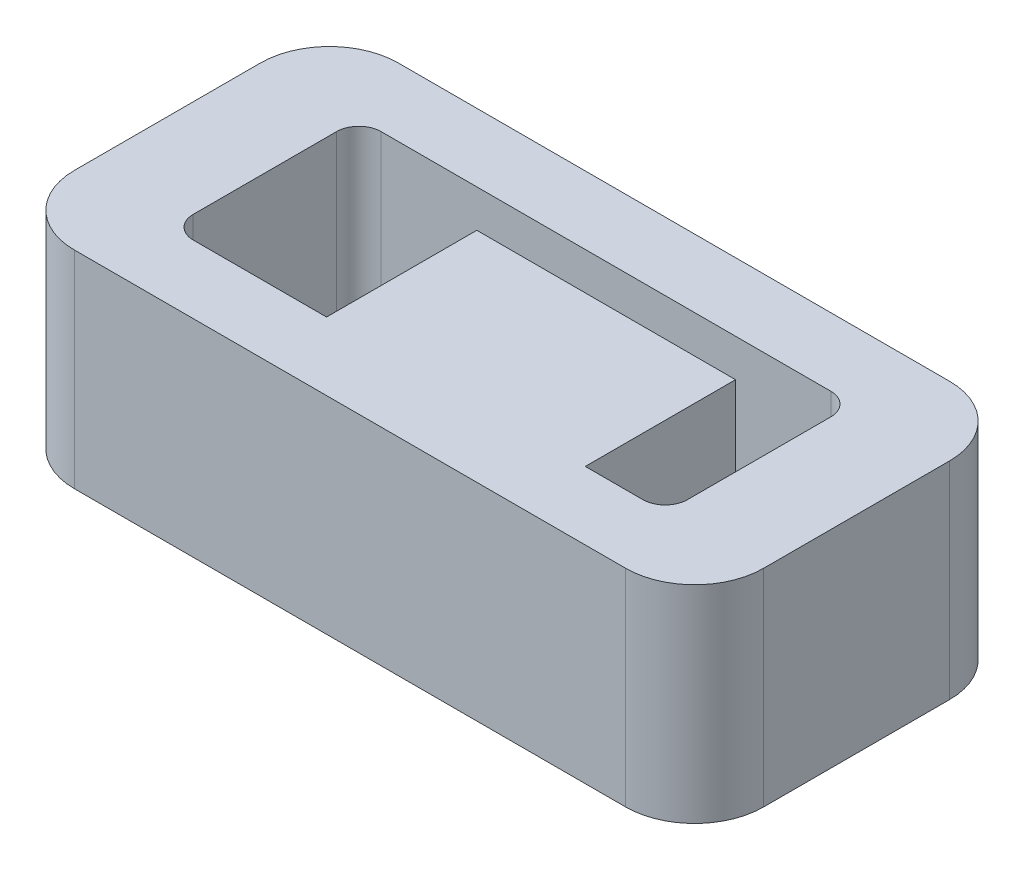
SolidWorks part; units mm, degrees
material "K110"
ref_plane "Front Plane" through (0, 0, 0) normal (0, 0, 1) x (1, 0, 0)
ref_plane "Top Plane" through (0, 0, 0) normal (0, 1, 0) x (1, 0, 0)
ref_plane "Right Plane" through (0, 0, 0) normal (1, 0, 0) x (0, 0, -1)
sketch "Sketch2" plane through (0, 0, 0) normal (0, 1, 0) x (1, 0, 0)
  line L1 (-50, -23.5) -> (50, -23.5)
  line L2 (-50, -23.5) -> (-50, 23.5)
  line L3 (-50, 23.5) -> (50, 23.5)
  line L4 (50, -23.5) -> (50, 23.5)
  line L5 (-50, -23.5) -> (50, 23.5) construction
  line L6 (-50, 23.5) -> (50, -23.5) construction
  point P0 (0, 0)
  dimension "D1" = 100
  dimension "D2" = 47
extrude "Boss-Extrude1" add sketch "Sketch2" against normal blind 30
fillet "Fillet1" radius 10 4 edges at (-50, -15, -23.5) (50, -15, -23.5) (50, -15, 23.5) (-50, -15, 23.5)
sketch "Sketch3" plane through (0, 0, 0) normal (0, 1, 0) x (1, 0, 0)
  line L16 (35.855, -10.4) -> (35.855, 10.4)
  line L17 (24.265, -13.63) -> (32.625, -13.63)
  line L18 (24.265, 8.17) -> (24.265, -13.63)
  line L19 (-13.275, 8.17) -> (24.265, 8.17)
  line L20 (-13.275, -13.63) -> (-13.275, 8.17)
  line L21 (-32.625, -13.63) -> (-13.275, -13.63)
  line L22 (-35.855, 10.4) -> (-35.855, -10.4)
  line L23 (32.625, 13.63) -> (-32.625, 13.63)
  line L24 (35.855, -10.4) -> (35.855, 10.4)
  line L25 (24.265, -13.63) -> (32.625, -13.63)
  line L26 (24.265, 8.17) -> (24.265, -13.63)
  line L27 (-13.275, 8.17) -> (24.265, 8.17)
  line L28 (-13.275, -13.63) -> (-13.275, 8.17)
  line L29 (-32.625, -13.63) -> (-13.275, -13.63)
  line L30 (-35.855, 10.4) -> (-35.855, -10.4)
  line L31 (32.625, 13.63) -> (-32.625, 13.63)
  arc A8 (35.855, 10.4) -> (32.625, 13.63) centre (32.625, 10.4) ccw
  arc A9 (32.625, -13.63) -> (35.855, -10.4) centre (32.625, -10.4) ccw
  arc A10 (-35.855, -10.4) -> (-32.625, -13.63) centre (-32.625, -10.4) ccw
  arc A11 (-32.625, 13.63) -> (-35.855, 10.4) centre (-32.625, 10.4) ccw
  arc A12 (35.855, 10.4) -> (32.625, 13.63) centre (32.625, 10.4) ccw
  arc A13 (32.625, -13.63) -> (35.855, -10.4) centre (32.625, -10.4) ccw
  arc A14 (-35.855, -10.4) -> (-32.625, -13.63) centre (-32.625, -10.4) ccw
  arc A15 (-32.625, 13.63) -> (-35.855, 10.4) centre (-32.625, 10.4) ccw
  dimension "D1" = 0.23
extrude "Cut-Extrude1" cut sketch "Sketch3" against normal up to next
hole_wizard "M6 Tapped Hole1" positions "Sketch6" profile "Sketch5" tap size "M6" standard "ISO"
sketch "Sketch6" plane through (0, -30, 0) normal (0, -1, 0) x (-1, 0, 0)
  line L0 (-50, -13.5) -> (-50, 13.5) construction
  line L1 (-40, 23.5) -> (40, 23.5) construction
  line L2 (40, -23.5) -> (-40, -23.5) construction
  line L3 (50, 13.5) -> (50, -13.5) construction
  point P0 (-43, 16.5)
  point P2 (43, 16.5)
  point P4 (43, -16.5)
  point P6 (-43, -16.5)
  point P9 (0, 0)
  point P10 (0, 0)
  point P11 (0, 0)
  point P12 (0, 0)
  dimension "D1" = 7
  dimension "D2" = 7
  dimension "D3" = 7
  dimension "D4" = 7
sketch "Sketch5" plane through (43, -30, -16.5) normal (1, 0, 0) x (0, 0, -1)
  line L0 (0, 0) -> (0, 18.5022)
  line L1 (0, 18.5022) -> (2.5, 17)
  line L2 (2.5, 17) -> (2.5, 0.525)
  line L3 (2.5, 0.525) -> (3.025, 0)
  line L5 (3.025, 0) -> (0, 0)
  line L6 (-2.5, 0.525) -> (-3.025, 0) construction
  line L10 (0, 18.5022) -> (-2.5, 17) construction
  line L11 (0, -6.35) -> (0, 107.95) construction
  dimension "Tap Drill Dia." = 5
  dimension "Tap Drill Depth" = 17
  dimension "Near C'Sink Dia." = 6.05
  dimension "Near C'Sink Angle" = 90
  dimension "Drill Angle" = 118
cosmetic thread "Hole Thread1"
cosmetic thread "Hole Thread2"
cosmetic thread "Hole Thread3"
cosmetic thread "Hole Thread4"
